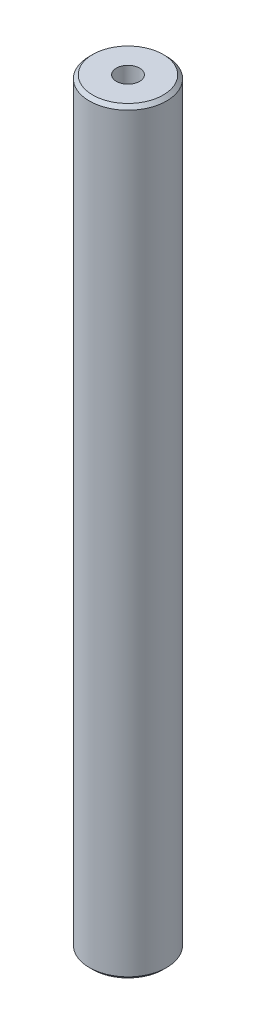
SolidWorks part; units mm, degrees
ref_plane "Front Plane" through (0, 0, 0) normal (0, 0, 1) x (1, 0, 0)
ref_plane "Top Plane" through (0, 0, 0) normal (0, 1, 0) x (1, 0, 0)
ref_plane "Right Plane" through (0, 0, 0) normal (1, 0, 0) x (0, 0, -1)
sketch "Sketch1" plane through (0, 0, 0) normal (0, 1, 0) x (1, 0, 0)
  circle A0 centre (0, 0) radius 17.5
  dimension "SHAFT_OD" = 35
extrude "Boss-Extrude1" add sketch "Sketch1" along normal blind 343.0581
sketch "Sketch2" plane through (0, 0, 0) normal (0, 1, 0) x (1, 0, 0)
  circle A0 centre (0, 0) radius 5.2518
  dimension "BORE_D" = 10.5036
extrude "Cut-Extrude1" cut sketch "Sketch2" along normal through all
chamfer "Chamfer1" distance 1.5545 angle 45 2 edges at (0, 343.0581, 17.5) (0, 0, 17.5)
